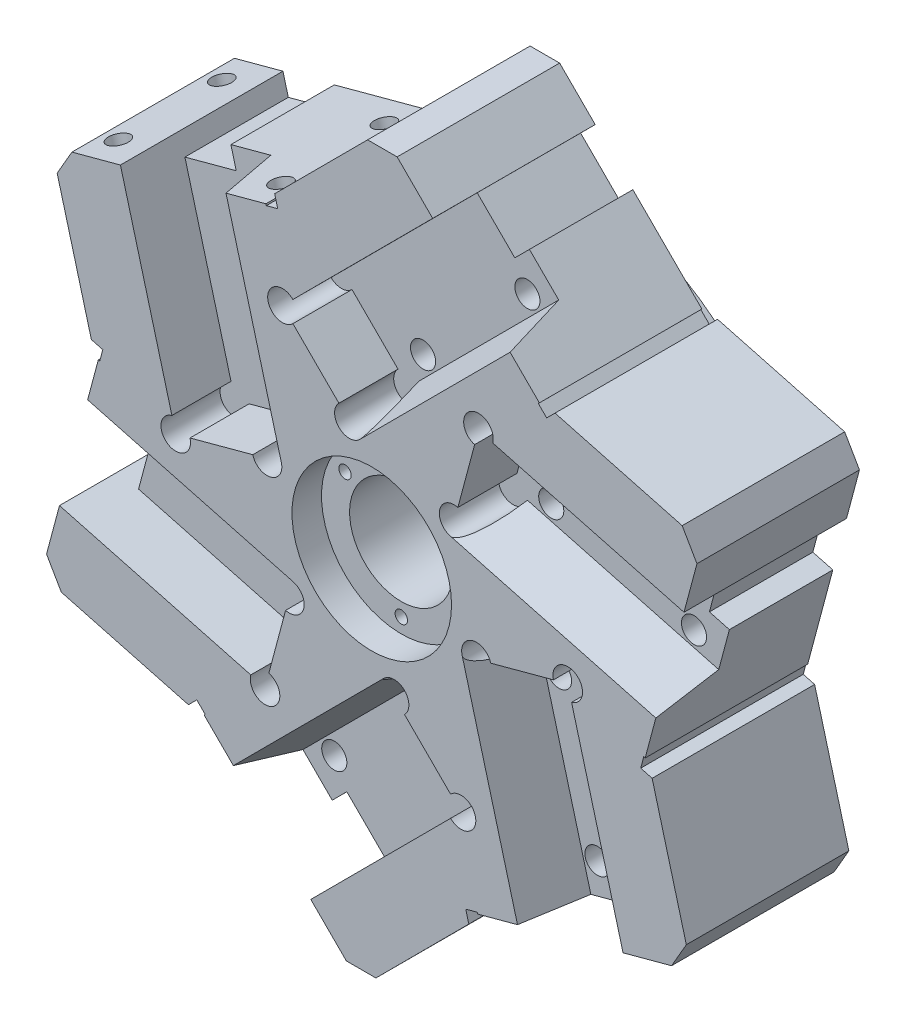
SolidWorks part; units mm, degrees
ref_plane "Front Plane" through (0, 0, 0) normal (0, 0, 1) x (1, 0, 0)
ref_plane "Top Plane" through (0, 0, 0) normal (0, 1, 0) x (1, 0, 0)
ref_plane "Right Plane" through (0, 0, 0) normal (1, 0, 0) x (0, 0, -1)
sketch "Sketch1" plane through (0, 0, 0) normal (0, 0, 1) x (1, 0, 0)
  line L1 (3.9553, 125) -> (-106.2755, 65.9254)
  line L2 (-106.2755, 65.9254) -> (-110.2308, -59.0746)
  line L3 (-110.2308, -59.0746) -> (-3.9553, -125)
  line L4 (-3.9553, -125) -> (106.2755, -65.9254)
  line L5 (106.2755, -65.9254) -> (110.2308, 59.0746)
  line L6 (110.2308, 59.0746) -> (3.9553, 125)
  circle A0 centre (0, 0) radius 108.3074 construction
  dimension "D2" = 216.6147
  dimension "D1" = 250
extrude "Boss-Extrude1" add sketch "Sketch1" along normal blind 55
sketch "Sketch3" plane through (0, 0, 55) normal (0, 0, 1) x (1, 0, 0)
  line L0 (110.2308, 59.0746) -> (3.9553, 125) construction
  line L1 (3.9553, 125) -> (-106.2755, 65.9254) construction
  line L2 (110.0583, 53.623) -> (115.0583, 62.2833)
  line L3 (115.0583, 62.2833) -> (105.0583, 62.2833)
  line L4 (110.0583, 53.623) -> (105.0583, 62.2833)
  line L5 (101.468, -68.5018) -> (111.468, -68.5018)
  line L6 (111.468, -68.5018) -> (106.468, -59.8415)
  line L7 (101.468, -68.5018) -> (106.468, -59.8415)
  line L8 (-8.5903, -122.1248) -> (-3.5903, -130.7851)
  line L9 (8.5903, 122.1248) -> (-1.4097, 122.1248)
  line L10 (8.5903, 122.1248) -> (3.5903, 130.7851)
  line L11 (3.5903, 130.7851) -> (-1.4097, 122.1248)
  line L12 (-3.5903, -130.7851) -> (1.4097, -122.1248)
  line L13 (-8.5903, -122.1248) -> (1.4097, -122.1248)
  line L14 (-110.0583, -53.623) -> (-115.0583, -62.2833)
  line L15 (-115.0583, -62.2833) -> (-105.0583, -62.2833)
  line L16 (-110.0583, -53.623) -> (-105.0583, -62.2833)
  line L17 (-101.468, 68.5018) -> (-111.468, 68.5018)
  line L26 (-111.468, 68.5018) -> (-106.468, 59.8415)
  line L27 (-101.468, 68.5018) -> (-106.468, 59.8415)
  circle A0 centre (0, 0) radius 88.5074 construction
  point P4 (3.5903, 122.1248)
  point P26 (0, 0)
  point P46 (0, 0)
  dimension "D4" = 177.0149
  dimension "D1" = 10
  dimension "D2" = 10
  dimension "D3" = 6
  dimension "D6" = 122.1248
  dimension "D5" = 113.5213
extrude "Cut-Extrude1" cut sketch "Sketch3" against normal through all
sketch "Sketch6" plane through (0, 0, 55) normal (0, 0, 1) x (1, 0, 0)
  line L0 (-1.4097, 122.1248) -> (-32.856, 90.6013)
  line L1 (-101.468, 68.5018) -> (-35.8067, 86.1821)
  line L2 (-1.4097, 122.1248) -> (-72.9544, 193.4941)
  line L3 (-72.9544, 193.4941) -> (-101.468, 68.5018)
  line L4 (-32.856, 90.6013) -> (-31.816, 86.7388)
  line L5 (-35.8067, 86.1821) -> (-35.6767, 85.6993)
  line L6 (-35.6767, 85.6993) -> (-31.816, 86.7388)
  line L8 (105.0583, 62.2833) -> (131.0936, 159.9275)
  line L9 (131.0936, 159.9275) -> (8.5903, 122.1248)
  line L10 (8.5903, 122.1248) -> (56.7325, 74.1006)
  line L11 (62.035, 73.7548) -> (59.21, 70.9229)
  line L12 (56.7325, 74.1006) -> (56.3794, 73.7466)
  line L13 (56.3794, 73.7466) -> (59.21, 70.9229)
  line L14 (105.0583, 62.2833) -> (62.035, 73.7548)
  line L15 (106.468, -59.8415) -> (204.0481, -33.5667)
  line L16 (204.0481, -33.5667) -> (110.0583, 53.623)
  line L17 (110.0583, 53.623) -> (92.5392, -12.0815)
  line L18 (94.891, -16.8465) -> (91.026, -15.816)
  line L19 (92.5392, -12.0815) -> (92.0561, -11.9527)
  line L20 (92.0561, -11.9527) -> (91.026, -15.816)
  line L21 (106.468, -59.8415) -> (94.891, -16.8465)
  line L22 (1.4097, -122.1248) -> (72.9544, -193.4941)
  line L23 (72.9544, -193.4941) -> (101.468, -68.5018)
  line L24 (101.468, -68.5018) -> (35.8067, -86.1821)
  line L25 (32.856, -90.6013) -> (31.816, -86.7388)
  line L26 (35.8067, -86.1821) -> (35.6767, -85.6993)
  line L27 (35.6767, -85.6993) -> (31.816, -86.7388)
  line L28 (1.4097, -122.1248) -> (32.856, -90.6013)
  line L29 (-105.0583, -62.2833) -> (-131.0936, -159.9275)
  line L30 (-131.0936, -159.9275) -> (-8.5903, -122.1248)
  line L31 (-8.5903, -122.1248) -> (-56.7325, -74.1006)
  line L32 (-62.035, -73.7548) -> (-59.21, -70.9229)
  line L33 (-56.7325, -74.1006) -> (-56.3794, -73.7466)
  line L34 (-56.3794, -73.7466) -> (-59.21, -70.9229)
  line L35 (-105.0583, -62.2833) -> (-62.035, -73.7548)
  line L36 (-106.468, 59.8415) -> (-204.0481, 33.5667)
  line L37 (-204.0481, 33.5667) -> (-110.0583, -53.623)
  line L38 (-110.0583, -53.623) -> (-92.5392, 12.0815)
  line L39 (-94.891, 16.8465) -> (-91.026, 15.816)
  line L40 (-92.5392, 12.0815) -> (-92.0561, 11.9527)
  line L41 (-92.0561, 11.9527) -> (-91.026, 15.816)
  line L42 (-106.468, 59.8415) -> (-94.891, 16.8465)
  point P48 (0, 0)
  dimension "D1" = 72
  dimension "D2" = 90
  dimension "D3" = 4
  dimension "D5" = 68
  dimension "D4" = 0.5
  dimension "D6" = 57.921
  dimension "D8" = 6
extrude "Cut-Extrude6" cut sketch "Sketch6" against normal through all
sketch "Sketch7" plane through (0, 0, 55) normal (0, 0, 1) x (1, 0, 0)
  line L0 (-85.0527, 72.9219) -> (-54.1533, 81.242)
  line L1 (-101.468, 68.5018) -> (-35.8067, 86.1821) construction
  line L2 (-54.1533, 81.242) -> (-36.733, 16.5463)
  line L3 (-40.261, 10.4182) -> (-61.5044, 4.6981)
  line L4 (-67.6324, 8.2262) -> (-85.0527, 72.9219)
  line L5 (-94.891, 16.8465) -> (-106.468, 59.8415) construction
  line L6 (-66.3324, 3.3981) -> (-67.6324, 8.2262) construction
  line L7 (-61.5044, 4.6981) -> (-66.3324, 3.3981) construction
  line L8 (-36.733, 16.5463) -> (-35.433, 11.7183) construction
  line L9 (-40.261, 10.4182) -> (-35.433, 11.7183) construction
  line L10 (43.281, 87.5191) -> (-4.037, 40.0849)
  line L11 (20.6258, 110.1187) -> (43.281, 87.5191)
  line L12 (-26.6922, 62.6845) -> (20.6258, 110.1187)
  line L13 (-11.1081, 40.0762) -> (-26.6835, 55.6134)
  line L14 (97.4343, 6.2771) -> (32.696, 23.5386)
  line L15 (105.6785, 37.1969) -> (97.4343, 6.2771)
  line L16 (40.9403, 54.4583) -> (105.6785, 37.1969)
  line L17 (29.153, 29.6579) -> (34.8209, 50.9153)
  line L18 (54.1533, -81.242) -> (36.733, -16.5463)
  line L19 (85.0527, -72.9219) -> (54.1533, -81.242)
  line L20 (67.6324, -8.2262) -> (85.0527, -72.9219)
  line L21 (40.261, -10.4182) -> (61.5044, -4.6981)
  line L22 (-43.281, -87.5191) -> (4.037, -40.0849)
  line L23 (-20.6258, -110.1187) -> (-43.281, -87.5191)
  line L24 (26.6922, -62.6845) -> (-20.6258, -110.1187)
  line L25 (11.1081, -40.0762) -> (26.6835, -55.6134)
  line L26 (-97.4343, -6.2771) -> (-32.696, -23.5386)
  line L27 (-105.6785, -37.1969) -> (-97.4343, -6.2771)
  line L28 (-40.9403, -54.4583) -> (-105.6785, -37.1969)
  line L29 (-29.153, -29.6579) -> (-34.8209, -50.9153)
  line L30 (-32.856, 90.6013) -> (-1.4097, 122.1248) construction
  line L31 (8.5903, 122.1248) -> (56.7325, 74.1006) construction
  arc A0 (-67.6324, 8.2262) -> (-61.5044, 4.6981) centre (-66.3324, 3.3981) ccw
  arc A1 (-40.261, 10.4182) -> (-36.733, 16.5463) centre (-35.433, 11.7183) ccw
  arc A2 (-26.6922, 62.6845) -> (-26.6835, 55.6134) centre (-30.2233, 59.1446) ccw
  arc A3 (-11.1081, 40.0762) -> (-4.037, 40.0849) centre (-7.5682, 36.545) ccw
  arc A4 (40.9403, 54.4583) -> (34.8209, 50.9153) centre (36.1091, 55.7465) ccw
  arc A5 (29.153, 29.6579) -> (32.696, 23.5386) centre (27.8648, 24.8267) ccw
  arc A6 (67.6324, -8.2262) -> (61.5044, -4.6981) centre (66.3324, -3.3981) ccw
  arc A7 (40.261, -10.4182) -> (36.733, -16.5463) centre (35.433, -11.7183) ccw
  arc A8 (26.6922, -62.6845) -> (26.6835, -55.6134) centre (30.2233, -59.1446) ccw
  arc A9 (11.1081, -40.0762) -> (4.037, -40.0849) centre (7.5682, -36.545) ccw
  arc A10 (-40.9403, -54.4583) -> (-34.8209, -50.9153) centre (-36.1091, -55.7465) ccw
  arc A11 (-29.153, -29.6579) -> (-32.696, -23.5386) centre (-27.8648, -24.8267) ccw
  point P57 (0, 0)
  dimension "D4" = 5
  dimension "D5" = 5
  dimension "D7" = 17.3615
  dimension "D1" = 32
  dimension "D2" = 17
  dimension "D3" = 72
  dimension "D6" = 6
extrude "Cut-Extrude7" cut sketch "Sketch7" against normal blind 20
sketch "Sketch8" plane through (0, 0, 55) normal (0, 0, 1) x (1, 0, 0)
  line L0 (15.6822, 105.1629) -> (25.7012, 115.2066)
  line L1 (3, 19.5) -> (-3, 19.5)
  line L2 (3, 19.5) -> (3, 17.2409)
  line L3 (20.6258, 110.1187) -> (-26.6922, 62.6845) construction
  line L4 (-3, 19.5) -> (-3, 17.2409)
  line L5 (25.7012, 115.2066) -> (38.4447, 102.4943)
  line L6 (38.4447, 102.4943) -> (28.4257, 92.4506)
  line L7 (28.4257, 92.4506) -> (15.6822, 105.1629)
  line L8 (43.281, 87.5191) -> (20.6258, 110.1187) construction
  line L9 (98.9148, 39.0003) -> (112.6224, 35.3454)
  line L10 (112.6224, 35.3454) -> (107.985, 17.953)
  line L11 (107.985, 17.953) -> (94.2774, 21.6079)
  line L12 (94.2774, 21.6079) -> (98.9148, 39.0003)
  line L13 (83.2327, -66.1626) -> (86.9212, -79.8612)
  line L14 (86.9212, -79.8612) -> (69.5403, -84.5413)
  line L15 (69.5403, -84.5413) -> (65.8518, -70.8427)
  line L16 (65.8518, -70.8427) -> (83.2327, -66.1626)
  line L17 (-15.6822, -105.1629) -> (-25.7012, -115.2066)
  line L18 (-25.7012, -115.2066) -> (-38.4447, -102.4943)
  line L19 (-38.4447, -102.4943) -> (-28.4257, -92.4506)
  line L20 (-28.4257, -92.4506) -> (-15.6822, -105.1629)
  line L21 (-98.9148, -39.0003) -> (-112.6224, -35.3454)
  line L22 (-112.6224, -35.3454) -> (-107.985, -17.953)
  line L23 (-107.985, -17.953) -> (-94.2774, -21.6079)
  line L24 (-94.2774, -21.6079) -> (-98.9148, -39.0003)
  line L25 (-83.2327, 66.1626) -> (-86.9212, 79.8612)
  line L26 (-86.9212, 79.8612) -> (-69.5403, 84.5413)
  line L27 (-69.5403, 84.5413) -> (-65.8518, 70.8427)
  line L28 (-65.8518, 70.8427) -> (-83.2327, 66.1626)
  line L29 (105.6785, 37.1969) -> (40.9403, 54.4583) construction
  line L30 (97.4343, 6.2771) -> (105.6785, 37.1969) construction
  arc A0 (-3, 17.2409) -> (3, 17.2409) centre (0, 0) ccw
  point P7 (0, 19.5)
  point P38 (0, 0)
  dimension "D1" = 35
  dimension "D2" = 2
  dimension "D3" = 6
  dimension "D4" = 18
  dimension "D5" = 7
  dimension "D6" = 14.1865
  dimension "D8" = 7
  dimension "D7" = 6
extrude "Cut-Extrude8" cut sketch "Sketch8" against normal through all
sketch "Sketch9" plane through (0, 0, 55) normal (0, 0, 1) x (1, 0, 0)
  circle A0 centre (0, 0) radius 27
  dimension "D1" = 54
extrude "Cut-Extrude9" cut sketch "Sketch9" against normal blind 10
hole_wizard "M5 Tapped Hole1" positions "Sketch12" profile "Sketch13" tap size "M5" standard "ISO"
sketch "Sketch12" plane through (0, 0, 45) normal (0, 0, 1) x (1, 0, 0)
  arc A1 (-3, 17.2409) -> (3, 17.2409) centre (0, 0) ccw construction
  point P0 (0, -22)
  dimension "D1" = 4.5
sketch "Sketch13" plane through (0, -22, 45) normal (1, 0, 0) x (0, -1, 0)
  line L0 (0, 0) -> (0, 26.2618)
  line L1 (0, 26.2618) -> (2.1, 25)
  line L2 (2.1, 25) -> (2.1, 0)
  line L5 (2.1, 0) -> (0, 0)
  line L10 (0, 26.2618) -> (-2.1, 25) construction
  line L11 (0, -6.35) -> (0, 107.95) construction
  dimension "Tap Drill Dia." = 4.2
  dimension "Tap Drill Depth" = 25
  dimension "Drill Angle" = 118
cosmetic thread "Hole Thread1" parameters "D1"=20, "D2"=5
pattern_circular "CirPattern1" count 3 every 120 about axis through (0, 0, 45) along (0, 0, -1) of "M5 Tapped Hole1"
sketch "Sketch14" plane through (-24.0577, 89.3457, 0) normal (-0.26, 0.9656, 0) x (0.9656, 0.26, 0)
  line L0 (-31.1676, -35) -> (-26.1676, -55)
  line L1 (-31.1676, -55) -> (-12.1676, -55) construction
  line L2 (-63.1676, 0) -> (-63.1676, -55) construction
  line L3 (-31.1676, -35) -> (-43.7536, -55)
  line L4 (-43.7536, -55) -> (-26.1676, -55)
  line L5 (-36.1676, -55) -> (-26.1676, -55) construction
  dimension "D1" = 37
  dimension "D2" = 57.818
extrude "Cut-Extrude10" cut sketch "Sketch14" against normal up to next
pattern_circular "CirPattern2" count 6 every 60 about axis through (0, 0, 55) along (0, 0, 1) of "Cut-Extrude10"
hole_wizard "M8x1.0 Tapped Hole1" positions "Sketch17" profile "Sketch16" tap size "M8x1.0" standard "ISO"
sketch "Sketch17" plane through (-24.0577, 89.3457, 0) normal (-0.26, 0.9656, 0) x (0.9656, 0.26, 0)
  line L0 (-87.2473, 0) -> (-87.2473, -55) construction
  line L1 (-80.1676, 0) -> (-63.1676, 0) construction
  point P0 (-74.2473, -10)
  dimension "D1" = 13
  dimension "D2" = 10
sketch "Sketch16" plane through (-95.7514, 70.0411, 10) normal (0, 0, 1) x (-0.9656, -0.26, 0)
  line L0 (0, 0) -> (0, 22.103)
  line L1 (0, 22.103) -> (3.5, 20)
  line L2 (3.5, 20) -> (3.5, 0)
  line L5 (3.5, 0) -> (0, 0)
  line L10 (0, 22.103) -> (-3.5, 20) construction
  line L11 (0, -6.35) -> (0, 107.95) construction
  dimension "Tap Drill Dia." = 7
  dimension "Tap Drill Depth" = 20
  dimension "Drill Angle" = 118
cosmetic thread "Hole Thread2" parameters "D1"=20, "D2"=8
pattern_linear "LPattern1" count 2 spacing 57 along (0.9656, 0.26, 0) count 2 spacing 35 along (0, 0, 1) of "M8x1.0 Tapped Hole1"
sketch "Sketch18" plane through (0, 0, 0) normal (0, 0, -1) x (-1, 0, 0)
  circle A0 centre (0, 0) radius 78.5
  circle A1 centre (0, 0) radius 76
  dimension "D1" = 157
  dimension "D2" = 2.5
extrude "Boss-Extrude2" add sketch "Sketch18" along normal blind 5
sketch "Sketch19" plane through (0, 0, -5) normal (0, 0, -1) x (-1, 0, 0)
  circle A0 centre (0, 0) radius 76
  circle A1 centre (0, 0) radius 81
  circle A3 centre (0, 0) radius 76 construction
  dimension "D1" = 5
extrude "Boss-Extrude3" add sketch "Sketch19" along normal blind 5
sketch "Sketch21" plane through (0, 0, -10) normal (0, 0, -1) x (-1, 0, 0)
  circle A0 centre (0, 0) radius 35
  dimension "D1" = 70
extrude "Cut-Extrude11" cut sketch "Sketch21" against normal blind 17
sketch "Sketch22" plane through (0, 0, 0) normal (0, 0, -1) x (-1, 0, 0)
  circle A0 centre (0, 0) radius 56
  dimension "D1" = 112
extrude "Cut-Extrude12" cut sketch "Sketch22" against normal blind 1.5
sketch "Sketch23" plane through (0, 0, 1.5) normal (0, 0, -1) x (-1, 0, 0)
  line L0 (0, 0) -> (0, 56) construction
  line L2 (3, 34.8712) -> (3, 55.9196)
  line L4 (-3, 34.8712) -> (-3, 55.9196)
  circle A0 centre (0, 0) radius 56 construction
  circle A1 centre (0, 0) radius 35 construction
  arc A2 (3, 55.9196) -> (-3, 55.9196) centre (0, 0) ccw
  arc A3 (3, 34.8712) -> (-3, 34.8712) centre (0, 0) ccw
  dimension "D1" = 6
extrude "Cut-Extrude13" cut sketch "Sketch23" against normal up to surface (5.5 mm away) up to face at (-35, 0, 7)
ref_plane "Plane1" through (0, 33.5, 0) normal (0, -1, 0) x (-1, 0, 0)
sketch "Sketch25" plane through (0, 33.5, 0) normal (0, -1, 0) x (-1, 0, 0)
  line L0 (3, -7) -> (9, -1.5)
  line L1 (3, -7) -> (3, -1.5) construction
  line L2 (35, -7) -> (-35, -7) construction
  line L3 (35, -1.5) -> (-35, -1.5) construction
  line L4 (-3, -7) -> (-3, -1.5) construction
  line L5 (9, -1.5) -> (2.3792, 0.7175)
  line L6 (2.3792, 0.7175) -> (3, -7)
  dimension "D1" = 12
  dimension "D2" = 66.884
  dimension "D3" = 6.9823
extrude "Cut-Extrude14" cut sketch "Sketch25" against normal up to surface (21.7721 mm away) up to face at (0, 27.9598, 4.25)
pattern_circular "CirPattern4" count 6 every 60 about axis through (0, 0, 7) along (0, 0, 1) of "Cut-Extrude13"
pattern_circular "CirPattern5" count 6 every 60 about axis through (0, 0, 7) along (0, 0, 1) of "Cut-Extrude14"
hole_wizard "CBORE for M6 Hex Head Bolt1" positions "Sketch27" profile "Sketch26" counterbore size "M6" standard "ISO"
sketch "Sketch27" plane through (0, 0, 1.5) normal (0, 0, -1) x (-1, 0, 0)
  line L0 (-22.125, 38.3216) -> (22.125, -38.3216) construction
  line L2 (44.25, 0) -> (-44.25, 0) construction
  arc A0 (-31.6993, 14.8375) -> (-31.6993, -14.8375) centre (0, 0) ccw construction
  arc A1 (-3, 34.8712) -> (-24.7916, 24.7058) centre (0, 0) ccw construction
  point P0 (-22.125, 38.3216)
  point P1 (-44.25, 0)
  point P3 (44.25, 0)
  point P5 (22.125, -38.3216)
  dimension "D1" = 60
  dimension "D2" = 9.25
  dimension "D3" = 9.25
sketch "Sketch26" plane through (22.125, 38.3216, 1.5) normal (1, 0, 0) x (0, 1, 0)
  line L0 (0, 0) -> (0, 21.9828)
  line L1 (0, 21.9828) -> (3.3, 20)
  line L2 (3.3, 20) -> (3.3, 4)
  line L3 (3.3, 4) -> (7.2735, 4)
  line L4 (7.2735, 4) -> (7.2735, 0)
  line L5 (7.2735, 0) -> (0, 0)
  line L10 (0, 21.9828) -> (-3.3, 20) construction
  line L11 (0, -6.35) -> (0, 107.95) construction
  dimension "Hole Dia." = 6.6
  dimension "Hole Depth" = 20
  dimension "C'Bore Dia." = 14.547
  dimension "C'Bore Depth" = 4
  dimension "Drill Angle" = 118
sketch "Sketch28" plane through (0, 0, 1.5) normal (0, 0, -1) x (-1, 0, 0)
  line L0 (19.75, 34.208) -> (-19.75, -34.208) construction
  line L1 (0, 0) -> (9.0589, 0) construction
  circle A0 centre (19.75, 34.208) radius 2.5
  circle A1 centre (-19.75, -34.208) radius 2.5
  arc A2 (28.6993, 20.0337) -> (9, 33.8231) centre (0, 0) ccw construction
  dimension "D1" = 2
  dimension "D2" = 5
  dimension "D3" = 60
extrude "Cut-Extrude15" cut sketch "Sketch28" against normal blind 10
sketch "Sketch29" plane through (0, 0, 0) normal (0, 0, -1) x (-1, 0, 0)
  line L0 (0, 0) -> (-31, 53.6936) construction
  line L1 (0, 0) -> (-23.3149, 0) construction
  circle A0 centre (-31, 53.6936) radius 4
  arc A1 (-3, 55.9196) -> (-43.367, 35.4303) centre (0, 0) ccw construction
  circle A2 centre (31, 53.6936) radius 4
  circle A3 centre (62, 0) radius 4
  circle A4 centre (31, -53.6936) radius 4
  circle A5 centre (-31, -53.6936) radius 4
  circle A6 centre (-62, 0) radius 4
  point P21 (0, 0)
  dimension "D1" = 8
  dimension "D2" = 2
  dimension "D5" = 62
  dimension "D3" = 60
  dimension "D6" = 62
  dimension "D4" = 6
extrude "Cut-Extrude16" cut sketch "Sketch29" against normal blind 12
hole_wizard "M10 Tapped Hole1" positions "Sketch31" profile "Sketch32" tap size "M10" standard "ISO"
sketch "Sketch31" plane through (0, 0, 35) normal (0, 0, 1) x (1, 0, 0)
  line L0 (-54.1533, 81.242) -> (-67.6718, 77.6019) construction
  line L1 (-83.2327, 66.1626) -> (-67.6324, 8.2262) construction
  line L2 (-56.3813, 70.2859) -> (-43.3811, 22.0055) construction
  line L4 (-56.3813, 70.2859) -> (-66.1935, 67.6438) construction
  line L6 (-83.2327, 66.1626) -> (-65.8518, 70.8427) construction
  point P0 (-56.3813, 70.2859)
  point P2 (-43.3811, 22.0055)
  dimension "D1" = 10
  dimension "D2" = 27
  dimension "D3" = 50
sketch "Sketch32" plane through (-56.3813, 70.2859, 35) normal (1, 0, 0) x (0, -1, 0)
  line L0 (0, 0) -> (0, 27.0537)
  line L1 (0, 27.0537) -> (4.25, 24.5)
  line L2 (4.25, 24.5) -> (4.25, 0)
  line L5 (4.25, 0) -> (0, 0)
  line L10 (0, 27.0537) -> (-4.25, 24.5) construction
  line L11 (0, -6.35) -> (0, 107.95) construction
  dimension "Tap Drill Dia." = 8.5
  dimension "Tap Drill Depth" = 24.5
  dimension "Drill Angle" = 118
cosmetic thread "Hole Thread3" parameters "D1"=20, "D2"=10
cosmetic thread "Hole Thread4" parameters "D1"=20, "D2"=10
pattern_circular "CirPattern6" count 6 every 60 about axis through (0, 0, 45) along (0, 0, -1) of "M10 Tapped Hole1"
